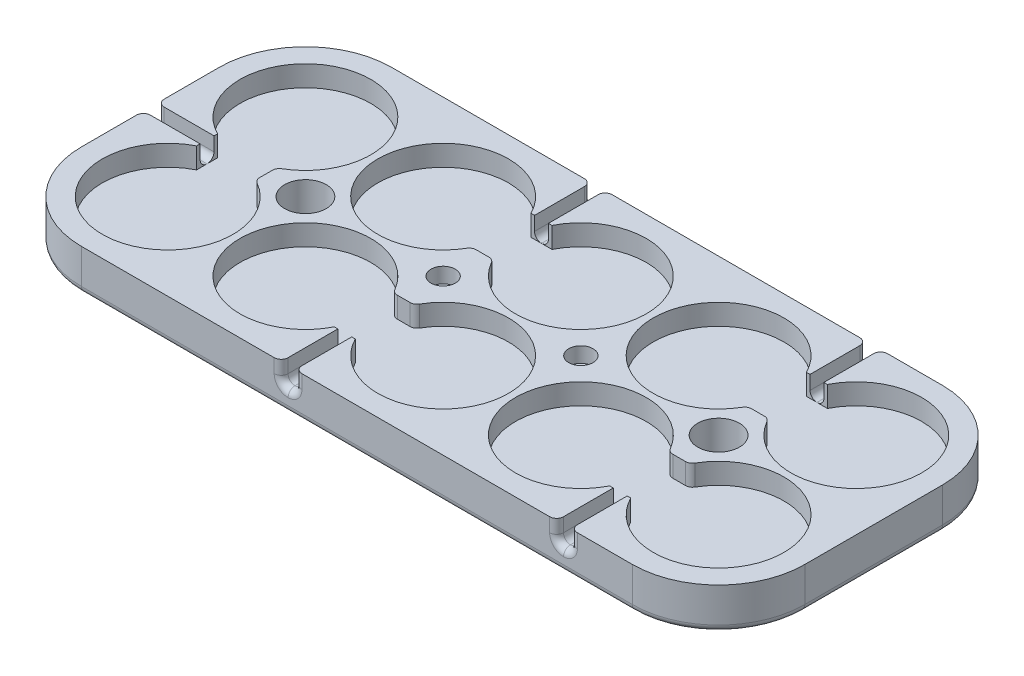
SolidWorks part; units mm, degrees
ref_plane "Front Plane" through (0, 0, 0) normal (0, 0, 1) x (1, 0, 0)
ref_plane "Top Plane" through (0, 0, 0) normal (0, 1, 0) x (1, 0, 0)
ref_plane "Right Plane" through (0, 0, 0) normal (1, 0, 0) x (0, 0, -1)
sketch "Sketch2" plane through (0, 0, 0) normal (0, 1, 0) x (1, 0, 0)
  line L0 (-39.7, 9.925) -> (-19.85, 9.925) construction
  line L1 (-19.85, 9.925) -> (0, 9.925) construction
  line L2 (0, 9.925) -> (19.85, 9.925) construction
  line L3 (19.85, 9.925) -> (39.7, 9.925) construction
  line L4 (39.7, 9.925) -> (39.7, -9.925) construction
  line L5 (39.7, -9.925) -> (19.85, -9.925) construction
  line L6 (19.85, -9.925) -> (0, -9.925) construction
  line L7 (0, -9.925) -> (-19.85, -9.925) construction
  line L8 (-39.7, 9.925) -> (-39.7, -9.925) construction
  line L9 (-39.7, -9.925) -> (-19.85, -9.925) construction
  line L10 (-39.7, 9.925) -> (39.7, -9.925) construction
  line L11 (-30.275, 9.925) -> (-29.275, 9.925) construction
  line L16 (-39.7, 0.5) -> (-39.7, -0.5) construction
  line L17 (-39.7, 22.35) -> (39.7, 22.35)
  line L19 (52.125, -9.925) -> (52.125, 9.925)
  line L20 (39.7, -22.35) -> (-39.7, -22.35)
  line L21 (-52.125, -9.925) -> (-52.125, 9.925)
  line L22 (-39.7, -9.925) -> (-52.125, -9.925) construction
  circle A0 centre (-39.7, 9.925) radius 9.425
  circle A1 centre (-19.85, 9.925) radius 9.425
  circle A2 centre (-39.7, -9.925) radius 9.425
  circle A3 centre (-19.85, -9.925) radius 9.425
  circle A4 centre (0, 9.925) radius 9.425
  circle A5 centre (0, -9.925) radius 9.425
  circle A6 centre (19.85, 9.925) radius 9.425
  circle A7 centre (19.85, -9.925) radius 9.425
  circle A8 centre (39.7, 9.925) radius 9.425
  circle A9 centre (39.7, -9.925) radius 9.425
  circle A10 centre (-39.7, 9.925) radius 12.425
  circle A11 centre (-39.7, -9.925) radius 12.425
  circle A12 centre (39.7, -9.925) radius 12.425
  circle A13 centre (39.7, 9.925) radius 12.425
  dimension "D1" = 18.85
  dimension "D2" = 1
  dimension "D3" = 1
  dimension "D4" = 3
extrude "Boss-Extrude1" add sketch "Sketch2" along normal blind 3 contours A13 L17 A10 A1 A11 A3 L20 A12 A7 A6 A5 A4 | A12 A13 A6 A8 | A13 A9 A12 A7 | A13 A12 L19 | A9 A13 A12 A8 | A11 A10 L21 | A11 A10 A1 A0 | A3 A11 A10 A2 | A10 A11 A0 A2 region at (-32.8744, 0, -19.9125) region at (0, 0, 0) region at (48.2539, 0, -18.4789) region at (-50.7094, 0, 0) region at (50.7094, 0, 0) region at (-50.5254, 0, 4.5259) region at (-39.7, 0, 0) region at (48.2539, 0, 18.4789) region at (39.7, 0, 0)
sketch "Sketch3" plane through (0, 0, 0) normal (0, 1, 0) x (1, 0, 0)
  line L0 (52.125, -9.925) -> (52.125, 9.925) construction
  line L1 (-52.125, -22.35) -> (52.125, -22.35)
  line L2 (-52.125, -22.35) -> (-52.125, 22.35)
  line L3 (-52.125, 22.35) -> (52.125, 22.35)
  line L4 (52.125, -22.35) -> (52.125, 22.35)
  line L5 (-52.125, -9.925) -> (-52.125, 9.925) construction
  line L6 (39.7, -22.35) -> (-39.7, -22.35) construction
  line L7 (-39.7, 22.35) -> (39.7, 22.35) construction
  circle A0 centre (-39.7, -9.925) radius 12.425
  circle A1 centre (-39.7, 9.925) radius 12.425
  circle A2 centre (39.7, 9.925) radius 12.425
  circle A3 centre (39.7, -9.925) radius 12.425
  circle A4 centre (-39.7, 9.925) radius 9.425 construction
  arc A5 (-39.7, 22.35) -> (-52.125, 9.925) centre (-39.7, 9.925) ccw construction
  arc A6 (-52.125, -9.925) -> (-39.7, -22.35) centre (-39.7, -9.925) ccw construction
  arc A7 (39.7, -22.35) -> (52.125, -9.925) centre (39.7, -9.925) ccw construction
  arc A8 (52.125, 9.925) -> (39.7, 22.35) centre (39.7, 9.925) ccw construction
extrude "Boss-Extrude2" add sketch "Sketch3" against normal blind 3 contours A3 A2 L3 A1 A0 L1 | A1 A0 | A0 A1 | A0 A1 | A1 L2 A0 | A3 A2 | A2 A3 | A3 A2 | A3 L4 A2 region at (0, 0, 0) region at (-39.7, 0, 11.0895) region at (-50.7094, 0, 0) region at (39.7, 0, 11.0895) region at (-39.7, 0, -11.0895) region at (-39.7, 0, 0) region at (39.7, 0, 0) region at (39.7, 0, -11.0895) region at (50.7094, 0, 0)
sketch "Sketch4" plane through (0, 0, 0) normal (0, 1, 0) x (1, 0, 0)
  line L1 (39.7, -5.675) -> (19.85, -5.675)
  line L2 (39.7, -5.675) -> (39.7, -14.175)
  line L3 (39.7, -14.175) -> (19.85, -14.175)
  line L4 (19.85, -5.675) -> (19.85, -14.175)
  line L5 (0, -5.675) -> (-19.85, -5.675)
  line L6 (0, -5.675) -> (0, -14.175)
  line L7 (0, -14.175) -> (-19.85, -14.175)
  line L8 (-19.85, -5.675) -> (-19.85, -14.175)
  line L9 (-43.95, -9.925) -> (-35.45, -9.925)
  line L10 (-43.95, -9.925) -> (-43.95, 9.925)
  line L11 (-43.95, 9.925) -> (-35.45, 9.925)
  line L12 (-35.45, -9.925) -> (-35.45, 9.925)
  line L13 (-19.85, 14.175) -> (0, 14.175)
  line L14 (-19.85, 14.175) -> (-19.85, 5.675)
  line L15 (-19.85, 5.675) -> (0, 5.675)
  line L16 (0, 14.175) -> (0, 5.675)
  line L17 (19.85, 14.175) -> (39.7, 14.175)
  line L18 (19.85, 14.175) -> (19.85, 5.675)
  line L19 (19.85, 5.675) -> (39.7, 5.675)
  line L20 (39.7, 14.175) -> (39.7, 5.675)
  circle A0 centre (-39.7, 9.925) radius 9.425 construction
  circle A1 centre (-39.7, -9.925) radius 9.425 construction
  circle A2 centre (-19.85, -9.925) radius 9.425 construction
  circle A3 centre (0, -9.925) radius 9.425 construction
  circle A4 centre (19.85, -9.925) radius 9.425 construction
  circle A5 centre (39.7, -9.925) radius 9.425 construction
  circle A6 centre (39.7, 9.925) radius 9.425 construction
  circle A7 centre (19.85, 9.925) radius 9.425 construction
  circle A8 centre (-19.85, 9.925) radius 9.425 construction
  circle A9 centre (0, 9.925) radius 9.425 construction
  point P20 (-39.7, 9.925)
  point P23 (-39.7, -9.925)
  point P26 (-19.85, -9.925)
  point P29 (0, -9.925)
  point P34 (19.85, -9.925)
  point P35 (39.7, -9.925)
  point P40 (39.7, 9.925)
  point P41 (19.85, 9.925)
  point P46 (-19.85, 9.925)
  point P47 (0, 9.925)
  dimension "D1" = 8.5
extrude "Cut-Extrude1" cut sketch "Sketch4" along normal through all
sketch "Sketch5" plane through (0, 0, 0) normal (0, 1, 0) x (1, 0, 0)
  line L0 (-52.125, -9.925) -> (-52.125, 9.925) construction
  line L1 (-10.925, 10.675) -> (-8.925, 10.675)
  line L2 (-10.925, 10.675) -> (-10.925, 22.35)
  line L3 (-10.925, 22.35) -> (-8.925, 22.35)
  line L4 (-8.925, 10.675) -> (-8.925, 22.35)
  line L5 (28.775, 10.675) -> (30.775, 10.675)
  line L6 (28.775, 10.675) -> (28.775, 22.35)
  line L7 (28.775, 22.35) -> (30.775, 22.35)
  line L8 (30.775, 10.675) -> (30.775, 22.35)
  line L9 (28.775, -10.675) -> (30.775, -10.675)
  line L10 (28.775, -10.675) -> (28.775, -22.35)
  line L11 (28.775, -22.35) -> (30.775, -22.35)
  line L12 (30.775, -10.675) -> (30.775, -22.35)
  line L13 (-10.925, -10.675) -> (-8.925, -10.675)
  line L14 (-10.925, -10.675) -> (-10.925, -22.35)
  line L15 (-10.925, -22.35) -> (-8.925, -22.35)
  line L16 (-8.925, -10.675) -> (-8.925, -22.35)
  line L17 (-40.45, -1) -> (-52.125, -1)
  line L18 (-40.45, -1) -> (-40.45, 1)
  line L19 (-40.45, 1) -> (-52.125, 1)
  line L20 (-52.125, -1) -> (-52.125, 1)
  line L21 (-39.7, 22.35) -> (39.7, 22.35) construction
  line L22 (39.7, -22.35) -> (-39.7, -22.35) construction
  line L23 (-35.45, 0) -> (-40.45, 0) construction
  line L24 (-35.45, -1.5126) -> (-35.45, 1.5126) construction
  line L25 (-9.925, -10.675) -> (-9.925, -5.675) construction
  line L26 (-8.4124, -5.675) -> (-11.4376, -5.675) construction
  line L27 (-9.925, 10.675) -> (-9.925, 5.675) construction
  line L28 (-11.4376, 5.675) -> (-8.4124, 5.675) construction
  line L29 (29.775, -10.675) -> (29.775, -5.675) construction
  line L30 (31.2876, -5.675) -> (28.2624, -5.675) construction
  line L31 (29.775, 10.675) -> (29.775, 5.675) construction
  line L32 (28.2624, 5.675) -> (31.2876, 5.675) construction
  dimension "D1" = 2
  dimension "D2" = 5
extrude "Cut-Extrude2" cut sketch "Sketch5" along normal through all
sketch "Sketch7" plane through (0, 0, 0) normal (0, 1, 0) x (1, 0, 0)
  line L0 (-29.775, 0) -> (-9.925, 0) construction
  line L1 (-9.925, 0) -> (9.925, 0) construction
  line L2 (9.925, 0) -> (29.775, 0) construction
  circle A1 centre (-29.775, 0) radius 3
  circle A2 centre (-9.925, 0) radius 1.75
  circle A3 centre (9.925, 0) radius 1.75
  circle A4 centre (29.775, 0) radius 3
  circle A5 centre (-29.775, 0) radius 4.6111 construction
  arc A6 (-11.4376, -5.675) -> (-11.4376, -14.175) centre (-19.85, -9.925) ccw construction
  arc A7 (-35.45, 1.5126) -> (-43.95, 1.5126) centre (-39.7, 9.925) ccw construction
  dimension "D1" = 6
  dimension "D2" = 3.5
extrude "Cut-Extrude3" cut sketch "Sketch7" along normal through all both and the other way through all
sketch "Sketch8" plane through (0, -3, 0) normal (0, -1, 0) x (1, 0, 0)
  circle A0 centre (9.925, 0) radius 3
  circle A1 centre (-9.925, 0) radius 3
  circle A2 centre (-9.925, 0) radius 1.75 construction
  circle A3 centre (9.925, 0) radius 1.75 construction
  circle A4 centre (29.775, 0) radius 3 construction
extrude "Cut-Extrude4" cut sketch "Sketch8" against normal blind 3.5
fillet "Fillet1" radius 1 35 edges at (28.775, 1.5, 22.35) (30.775, 1.5, 22.35) (-10.925, 1.5, 22.35) (-8.925, 1.5, 22.35) (-52.125, 1.5, 1) (-52.125, 1.5, -1) (-8.925, 1.5, -22.35) (-10.925, 1.5, -22.35) (30.775, 1.5, -22.35) (28.775, 1.5, -22.35) (29.775, 0, 22.35) (28.775, 0, 18.2625) (30.775, 0, 18.2625) (-9.925, 0, 22.35) (-8.925, 0, 18.2625) (-10.925, 0, 18.2625) (-48.0375, 0, 1) (-48.0375, 0, -1) (-52.125, 0, 0) (-9.925, 0, -22.35) (-10.925, 0, -18.2625) (-8.925, 0, -18.2625) (29.775, 0, -22.35) (28.775, 0, -18.2625) (30.775, 0, -18.2625) (28.2624, 1.5, 5.675) (31.2876, 1.5, 5.675) (-8.4124, 1.5, 5.675) (-11.4376, 1.5, 5.675) (-35.45, 1.5, -1.5126) (-35.45, 1.5, 1.5126) (-11.4376, 1.5, -5.675) (-8.4124, 1.5, -5.675) (28.2624, 1.5, -5.675) (31.2876, 1.5, -5.675)
fillet "Fillet2" radius 1 8 edges at (-48.4858, -3, 18.7108) (-52.125, -3, 0) (-48.4858, -3, -18.7108) (0, -3, -22.35) (48.4858, -3, -18.7108) (52.125, -3, 0) (48.4858, -3, 18.7108) (0, -3, 22.35)
sketch "Sketch9" plane through (0, -3, 0) normal (0, -1, 0) x (1, 0, 0)
  line L0 (-48.5919, 6.8) -> (-30.8081, 6.8) construction
  line L2 (-28.7419, 13.05) -> (8.8919, 13.05) construction
  line L4 (10.9581, 13.05) -> (48.5919, 13.05) construction
  line L5 (-48.5919, -13.05) -> (-30.8081, -13.05) construction
  line L6 (-28.7419, -13.05) -> (8.8919, -13.05) construction
  line L8 (10.9581, -13.05) -> (48.5919, -13.05) construction
  line L10 (-48.5919, 13.05) -> (-30.8081, 13.05) construction
  line L11 (-39.7, 13.05) -> (-39.7, 6.8) construction
  line L12 (-48.5919, -6.8) -> (-30.8081, -6.8) construction
  line L13 (-39.7, -6.8) -> (-39.7, -13.05) construction
  line L14 (-42.825, -18.8169) -> (-42.825, 18.8169) construction
  line L15 (-36.575, -18.8169) -> (-36.575, 18.8169) construction
  line L16 (-36.575, 0) -> (-42.825, 0) construction
  line L17 (-39.7, -6.8) -> (-39.7, 0) construction
  circle A0 centre (39.7, 9.925) radius 9.425 construction
  circle A1 centre (19.85, 9.925) radius 9.425 construction
  circle A2 centre (0, 9.925) radius 9.425 construction
  circle A3 centre (-19.85, 9.925) radius 9.425 construction
  circle A4 centre (-39.7, 9.925) radius 9.425 construction
  circle A5 centre (-39.7, -9.925) radius 9.425 construction
  circle A6 centre (-19.85, -9.925) radius 9.425 construction
  circle A7 centre (0, -9.925) radius 9.425 construction
  circle A8 centre (19.85, -9.925) radius 9.425 construction
  circle A9 centre (39.7, -9.925) radius 9.425 construction
  arc A10 (31.5574, 5.1786) -> (31.2876, 14.175) centre (39.7, 9.925) ccw construction
  arc A11 (28.2624, 14.175) -> (27.9926, 5.1786) centre (19.85, 9.925) ccw construction
  arc A12 (-8.1426, 5.1786) -> (-8.4124, 14.175) centre (0, 9.925) ccw construction
  arc A13 (-11.4376, 14.175) -> (-11.7074, 5.1786) centre (-19.85, 9.925) ccw construction
  arc A14 (-34.9536, 1.7824) -> (-43.95, 1.5126) centre (-39.7, 9.925) ccw construction
  arc A15 (-43.95, -1.5126) -> (-34.9536, -1.7824) centre (-39.7, -9.925) ccw construction
  arc A16 (-11.7074, -5.1786) -> (-11.4376, -14.175) centre (-19.85, -9.925) ccw construction
  arc A17 (-8.4124, -14.175) -> (-8.1426, -5.1786) centre (0, -9.925) ccw construction
  arc A18 (27.9926, -5.1786) -> (28.2624, -14.175) centre (19.85, -9.925) ccw construction
  arc A19 (31.2876, -14.175) -> (31.5574, -5.1786) centre (39.7, -9.925) ccw construction
  text T0 "<b>5+</b>" font "Arial Rounded MT Bold" height 6.5
  text T2 "<b>3+</b>" font "Arial Rounded MT Bold" height 6.5
  text T4 "<b>1+</b>" font "Arial Rounded MT Bold" height 6.5
  text T7 "<b>7+</b>" font "Arial Rounded MT Bold" height 6.5
  text T9 "<b>9+</b>" font "Arial Rounded MT Bold" height 6.5
  dimension "D1" = 6.25
  dimension "D2" = 6.25
  dimension "D3" = 6.25
extrude "Cut-Extrude5" cut sketch "Sketch9" against normal blind 0.5
sketch "Sketch10" plane through (0, 0.5, 0) normal (0, -1, 0) x (1, 0, 0)
  circle A0 centre (9.925, 0) radius 3
  circle A1 centre (-9.925, 0) radius 3
extrude "Boss-Extrude3" add sketch "Sketch10" against normal blind 0.3
